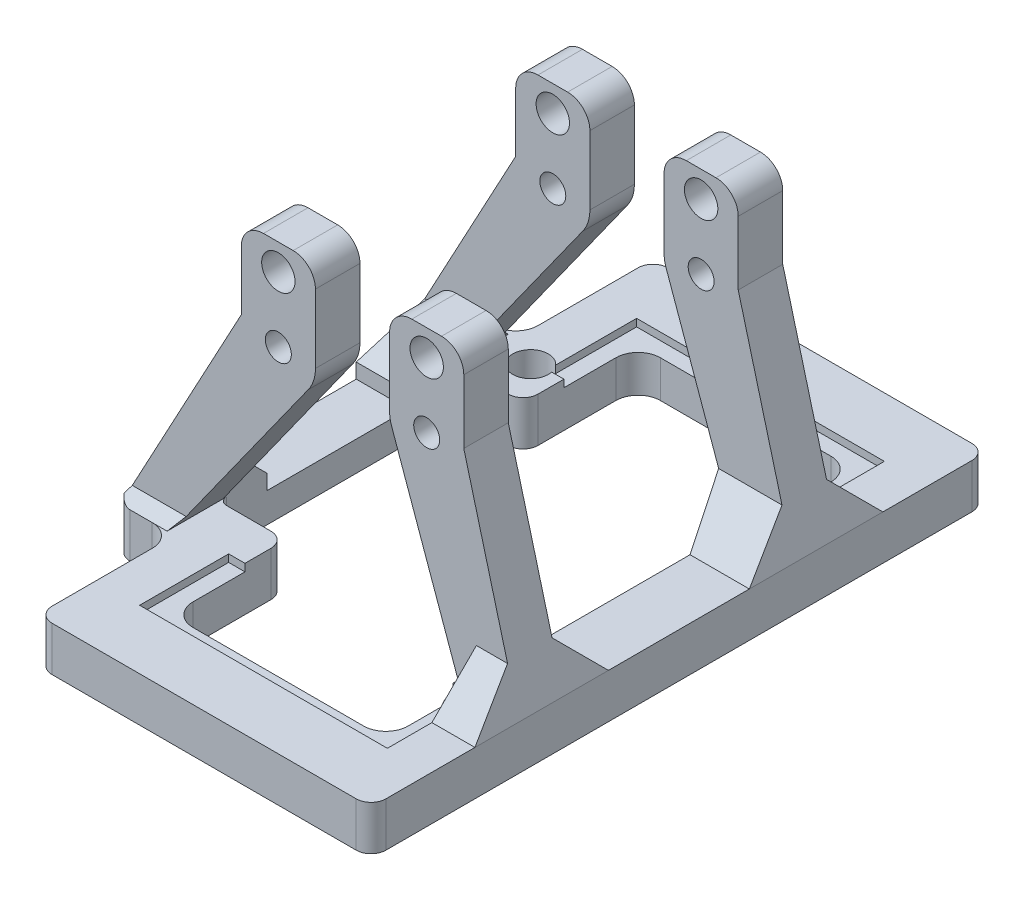
SolidWorks part; units mm, degrees
ref_plane "前视基准面" through (0, 0, 0) normal (0, 0, 1) x (1, 0, 0)
ref_plane "上视基准面" through (0, 0, 0) normal (0, 1, 0) x (1, 0, 0)
ref_plane "右视基准面" through (0, 0, 0) normal (1, 0, 0) x (0, 0, -1)
other "Configuration Table"
sketch "草图1" plane through (0, 0, 0) normal (0, 1, 0) x (1, 0, 0)
  line L0 (0, -76) -> (0, -106)
  line L1 (0, 0) -> (45, 0)
  line L2 (0, 0) -> (0, -30)
  line L3 (0, -106) -> (45, -106)
  line L4 (45, 0) -> (45, -106)
  line L5 (8, -21.5) -> (37, -21.5)
  line L6 (8, -21.5) -> (8, -37)
  line L7 (8, -84.5) -> (37, -84.5)
  line L8 (37, -21.5) -> (37, -84.5)
  line L9 (0, -30) -> (-8, -30)
  line L11 (0, -76) -> (-8, -76)
  line L12 (-8, -30) -> (-8, -76)
  line L13 (8, -69) -> (8, -84.5)
  line L14 (8, -37) -> (-1, -37)
  line L16 (8, -69) -> (-1, -69)
  line L17 (-1, -37) -> (-1, -69)
  circle A0 centre (4, -32) radius 1.75
  circle A1 centre (41, -74) radius 1.75
  dimension "D8" = 3.5
  dimension "D12" = 3.5
  dimension "D13" = 8
  dimension "D1" = 106
  dimension "D2" = 45
  dimension "D3" = 21.5
  dimension "D4" = 21.5
  dimension "D5" = 8
  dimension "D6" = 8
  dimension "D7" = 32
  dimension "D9" = 74
  dimension "D10" = 4
  dimension "D11" = 4
  dimension "D14" = 30
  dimension "D15" = 30
  dimension "D16" = 7
  dimension "D17" = 7
  dimension "D18" = 7
extrude "凸台-拉伸1" add sketch "草图1" along normal blind 6
sketch "草图3" plane through (0, 6, 0) normal (0, 1, 0) x (1, 0, 0)
  line L0 (45, -106) -> (45, 0) construction
  line L1 (0, -106) -> (45, -106)
  line L2 (0, -106) -> (0, -94.5)
  line L3 (0, -94.5) -> (45, -94.5)
  line L4 (45, -106) -> (45, -94.5)
  line L5 (37, -21.5) -> (8, -21.5) construction
  line L6 (0, 0) -> (45, 0)
  line L7 (0, 0) -> (0, -11.5)
  line L8 (0, -11.5) -> (45, -11.5)
  line L9 (45, 0) -> (45, -11.5)
  line L10 (8, -84.5) -> (37, -84.5) construction
  dimension "D1" = 10
  dimension "0" = 10
extrude "切除-拉伸1" cut sketch "草图3" against normal blind 10
sketch "草图4" plane through (0, 6, 0) normal (0, 1, 0) x (1, 0, 0)
  line L0 (45, -71) -> (45, -77)
  line L1 (45, -94.5) -> (45, -11.5) construction
  arc A0 (45, -71) -> (45, -77) centre (41, -74) ccw
  circle A1 centre (41, -74) radius 1.75
  dimension "D1" = 10
extrude "凸台-拉伸3" add sketch "草图4" against normal blind 6
sketch "草图13" plane through (0, 6, 0) normal (0, 1, 0) x (1, 0, 0)
  circle A0 centre (41, -74) radius 1.75
extrude "凸台-拉伸6" add sketch "草图13" against normal blind 0.5
sketch "草图14" plane through (0, 0, 0) normal (0, -1, 0) x (-1, 0, 0)
  circle A0 centre (-41, -74) radius 2.4
  dimension "D1" = 4.8
extrude "切除-拉伸8" cut sketch "草图14" against normal blind 4.5
sketch "草图15" plane through (0, 6, 0) normal (0, 1, 0) x (1, 0, 0)
  circle A0 centre (4, -32) radius 2.4
  dimension "D1" = 4.8
extrude "切除-拉伸9" cut sketch "草图15" against normal blind 4.5
ref_plane "基准面1" through (0, 0, 68.5) normal (0, 0, 1) x (1, 0, 0)
sketch "草图5" plane through (0, 0, 68.5) normal (0, 0, 1) x (1, 0, 0)
  line L0 (45, 6) -> (37.5, 34.1545)
  line L1 (37, 6) -> (27.8572, 31.6442)
  line L3 (-8, 6) -> (7.5, 34.7615)
  line L4 (-1, 6) -> (16.5, 30.5)
  line L5 (13.5784, 30.5) -> (17.5, 30.5) construction
  line L6 (-8, 6) -> (-1, 6)
  line L7 (37, 6) -> (45, 6)
  line L8 (37.5, 48.5) -> (37.5, 30.9) construction
  line L14 (27.5, 33.5) -> (27.5, 45.7615)
  line L15 (27.5, 45.7615) -> (37.5, 45.7615)
  line L16 (37.5, 34.1453) -> (37.5, 45.7615)
  line L17 (17.5, 23.9) -> (17.5, 48.5) construction
  line L19 (7.5, 34.7615) -> (7.5, 45.7615)
  line L20 (7.5, 45.7615) -> (17.5, 45.7615)
  line L21 (17.5, 33.5) -> (17.5, 45.7615)
  arc A0 (27.5, 33.5) -> (27.8572, 31.6442) centre (32.5, 33.5) ccw
  arc A2 (16.5, 30.5) -> (17.5, 33.5) centre (12.5, 33.5) ccw
  dimension "D1" = 11
  dimension "D2" = 10
  dimension "D3" = 0
extrude "凸台-拉伸4" add sketch "草图5" along normal blind 6 and the other way blind 37 contours L3 L6 L4 | A0 L1 L7 L0 | L0 A0 L1 region at (35.2194, 26.634, 68.5) region at (7.2781, 26.9278, 68.5)
sketch "草图11" plane through (0, 6, 0) normal (0, 1, 0) x (1, 0, 0)
  line L0 (-8, -31.5) -> (-8, -74.5) construction
  line L1 (-8, -37.5) -> (45, -37.5)
  line L2 (-8, -37.5) -> (-8, -68.5)
  line L3 (-8, -68.5) -> (45, -68.5)
  line L4 (45, -37.5) -> (45, -68.5)
  line L5 (45, -31.5) -> (45, -74.5) construction
  line L6 (-8, -74.5) -> (-1, -74.5) construction
  line L7 (-8, -31.5) -> (-1, -31.5) construction
  dimension "D1" = 6
  dimension "D2" = 6
extrude "切除-拉伸6" cut sketch "草图11" along normal through all
sketch "草图7" plane through (0, 0, 74.5) normal (0, 0, 1) x (1, 0, 0)
  circle A0 centre (12.5, 33.5) radius 1.75
  circle A1 centre (32.5, 33.5) radius 1.75
  dimension "D1" = 3.5
  dimension "D2" = 3.5
extrude "切除-拉伸2" cut sketch "草图7" against normal through all
chamfer "倒角5" distance 6 angle 45 6 edges at (41, 6, 37.5) (41, 6, 68.5) (-4.5, 6, 68.5) (-4.5, 6, 37.5) (41, 6, 74.5) (41, 6, 31.5)
chamfer "倒角7" distance 1.5 angle 45 2 edges at (-4.5, 6, 31.5) (-4.5, 6, 74.5)
sketch "草图12" plane through (0, 0, 0) normal (0, -1, 0) x (1, 0, 0)
  line L0 (3.2857, 68.5) -> (16.5, 68.5) construction
  line L1 (14.3746, 68.5) -> (-1, 68.5)
  line L2 (14.3746, 68.5) -> (14.3746, 37.5)
  line L3 (14.3746, 37.5) -> (-1, 37.5)
  line L4 (-1, 68.5) -> (-1, 37.5)
  line L5 (16.5, 37.5) -> (3.2857, 37.5) construction
  line L6 (-1, 37) -> (-1, 69) construction
  dimension "D1" = 0
extrude "切除-拉伸7" cut sketch "草图12" against normal through all
fillet "圆角6" radius 1 2 edges at (-1, 3, 37) (-1, 3, 69)
fillet "圆角1" radius 3 6 edges at (0, 3, 30) (0, 3, 76) (8, 3, 84.5) (37, 3, 84.5) (37, 3, 21.5) (8, 3, 21.5)
fillet "圆角2" radius 2 8 edges at (-8, 3, 76) (-8, 3, 30) (0, 3, 11.5) (45, 3, 11.5) (45, 3, 94.5) (0, 3, 94.5) (8, 3, 37) (8, 3, 69)
sketch "草图16" plane through (0, 0, 74.5) normal (0, 0, 1) x (1, 0, 0)
  line L0 (7.5, 45.7615) -> (17.5, 45.7615) construction
  line L1 (27.5, 45.7615) -> (37.5, 45.7615) construction
  circle A0 centre (12.5, 42.2615) radius 2.25
  circle A1 centre (32.5, 42.2615) radius 2.25
  dimension "D3" = 4.5
  dimension "D4" = 4.5
  dimension "D1" = 3.5
  dimension "D2" = 3.5
extrude "切除-拉伸10" cut sketch "草图16" against normal through all
fillet "圆角7" radius 3 8 edges at (37.5, 45.7615, 71.5) (27.5, 45.7615, 71.5) (17.5, 45.7615, 71.5) (7.5, 45.7615, 71.5) (37.5, 45.7615, 34.5) (27.5, 45.7615, 34.5) (17.5, 45.7615, 34.5) (7.5, 45.7615, 34.5)
sketch "草图17" plane through (0, 6, 0) normal (0, 1, 0) x (1, 0, 0)
  line L0 (8, -71) -> (8, -81.5) construction
  line L1 (5.8, -19.5) -> (39.2, -19.5)
  line L2 (5.8, -19.5) -> (5.8, -31.5)
  line L3 (5.8, -31.5) -> (39.2, -31.5)
  line L4 (39.2, -19.5) -> (39.2, -31.5)
  line L5 (5.8, -86.5) -> (39.2, -86.5)
  line L6 (5.8, -86.5) -> (5.8, -74.5)
  line L7 (5.8, -74.5) -> (39.2, -74.5)
  line L8 (39.2, -86.5) -> (39.2, -74.5)
  line L9 (37, -80.5) -> (37, -77) construction
  line L10 (11, -84.5) -> (34, -84.5) construction
  line L11 (8, -24.5) -> (8, -35) construction
  line L12 (37, -43.5) -> (37, -25.5) construction
  line L13 (34, -21.5) -> (11, -21.5) construction
  dimension "D1" = 2.2
  dimension "D2" = 2.2
  dimension "D3" = 2
  dimension "D4" = 12
  dimension "D5" = 2.2
  dimension "D6" = 2.2
  dimension "D7" = 2
  dimension "D8" = 12
extrude "切除-拉伸11" cut sketch "草图17" along normal through all and the other way blind 1
sketch "草图18" plane through (0, 6, 0) normal (0, 1, 0) x (1, 0, 0)
  line L1 (-8, -43.5) -> (-1, -43.5)
  line L2 (-8, -43.5) -> (-8, -62.5)
  line L3 (-8, -62.5) -> (-1, -62.5)
  line L4 (-1, -43.5) -> (-1, -62.5)
extrude "切除-拉伸12" cut sketch "草图18" against normal blind 2
